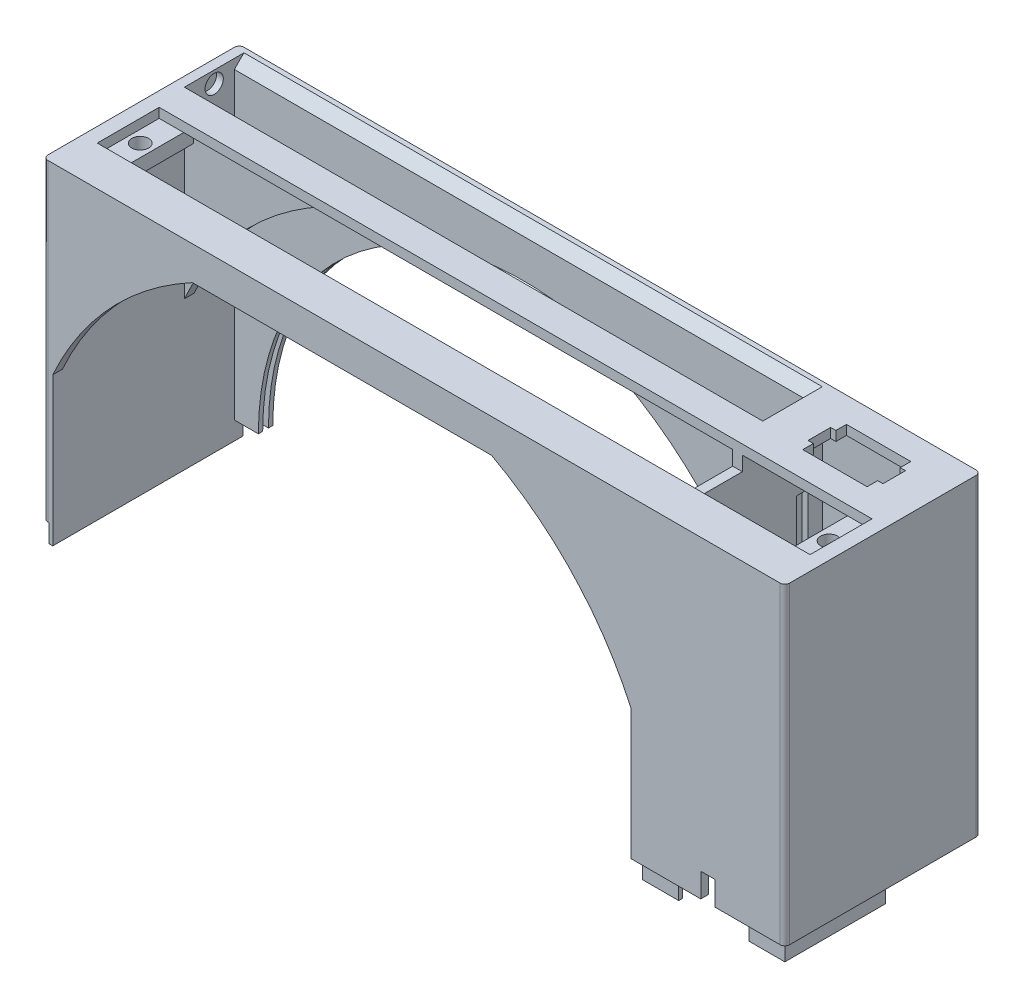
SolidWorks part; units mm, degrees
ref_plane "Plan de face" through (0, 0, 0) normal (0, 0, 1) x (1, 0, 0)
ref_plane "Plan de dessus" through (0, 0, 0) normal (0, 1, 0) x (1, 0, 0)
ref_plane "Plan de droite" through (0, 0, 0) normal (1, 0, 0) x (0, 0, -1)
sketch "Esquisse1" plane through (0, 0, 0) normal (0, 1, 0) x (1, 0, 0)
  line L1 (0, 0) -> (154.4, 0)
  line L2 (0, 0) -> (0, 40.8)
  line L3 (0, 40.8) -> (154.4, 40.8)
  line L4 (154.4, 0) -> (154.4, 40.8)
  dimension "D1" = 154.4
  dimension "D2" = 40.8
extrude "Boss.-Extru.1" add sketch "Esquisse1" against normal blind 2
sketch "Esquisse2" plane through (0, -2, 0) normal (0, -1, 0) x (1, 0, 0)
  line L0 (2, -2) -> (2, -27.4)
  line L1 (0, 0) -> (154.4, 0)
  line L2 (0, 0) -> (0, -40.8)
  line L3 (0, -40.8) -> (154.4, -40.8)
  line L4 (154.4, 0) -> (154.4, -40.8)
  line L7 (2, -2) -> (122.4, -2)
  line L8 (2, -29.4) -> (2, -37.8)
  line L9 (2, -29.4) -> (122.4, -29.4)
  line L11 (2, -27.4) -> (122.4, -27.4)
  line L13 (122.4, -27.4) -> (122.4, -2)
  line L14 (2, -2) -> (2, -38.8) construction
  line L16 (122.4, -37.8) -> (122.4, -29.4)
  line L19 (154.4, -40.8) -> (0, -40.8) construction
  line L20 (122.4, -37.8) -> (2, -37.8)
  line L21 (152.4, -2) -> (152.4, -38.8) construction
  line L22 (2, -2) -> (152.4, -2) construction
  line L23 (2, -38.8) -> (152.4, -38.8) construction
  line L24 (124.4, -37.8) -> (152.4, -37.8)
  line L25 (124.4, -37.8) -> (124.4, -2)
  line L26 (124.4, -2) -> (152.4, -2)
  line L27 (152.4, -37.8) -> (152.4, -2)
  dimension "D2" = 2
  dimension "D3" = 25.4
  dimension "D4" = 2
  dimension "D5" = 120.4
  dimension "D6" = 2
  dimension "D7" = 3
  dimension "D8" = 2
  dimension "D9" = 3
  dimension "D1" = 2
extrude "Boss.-Extru.2" add sketch "Esquisse2" along normal blind 63.2
sketch "Esquisse3" plane through (0, 0, 0) normal (0, 0, 1) x (1, 0, 0)
  line L0 (0, -65.2) -> (154.4, -65.2) construction
  line L1 (0, -65.2) -> (0, 0) construction
  line L4 (93.3249, -7) -> (31.0751, -7)
  line L7 (122.4, -65.2) -> (2, -65.2)
  line L8 (2, -38.1452) -> (2, -65.2)
  line L9 (62.2, -65.2) -> (62.2, -7) construction
  line L10 (122.4, -38.1452) -> (122.4, -65.2)
  arc A0 (31.0751, -7) -> (2, -38.1452) centre (62.2, -65.2) ccw
  arc A1 (122.4, -38.1452) -> (93.3249, -7) centre (62.2, -65.2) ccw
  point P13 (62.2, 0.8)
  dimension "D1" = 132
  dimension "D2" = 60.2
  dimension "D3" = 2
  dimension "D4" = 58.2
extrude "Enlèv. mat.-Extru.1" cut sketch "Esquisse3" against normal up to surface (29.4 mm away) up to face at (62.2, -33.6, -29.4)
sketch "Esquisse8" plane through (0, 0, -2) normal (0, 0, -1) x (-1, 0, 0)
  line L0 (-152.4, -65.2) -> (-152.4, -2) construction
  line L1 (-142.9, -56.4) -> (-133.9, -56.4)
  line L2 (-142.9, -56.4) -> (-142.9, -65.2)
  line L3 (-142.9, -65.2) -> (-133.9, -65.2)
  line L4 (-133.9, -56.4) -> (-133.9, -65.2)
  line L6 (-152.4, -65.2) -> (-124.4, -65.2) construction
  dimension "D1" = 9.5
  dimension "D2" = 9
  dimension "D3" = 8.8
extrude "Enlèv. mat.-Extru.3" cut sketch "Esquisse8" against normal blind 0.4
sketch "Esquisse9" plane through (0, 0, -1.6) normal (0, 0, -1) x (-1, 0, 0)
  line L0 (-142.9, -65.2) -> (-133.9, -65.2) construction
  line L1 (-139.9, -65.2) -> (-136.9, -65.2)
  line L2 (-139.9, -65.2) -> (-139.9, -60.2)
  line L3 (-139.9, -60.2) -> (-136.9, -60.2)
  line L4 (-136.9, -65.2) -> (-136.9, -60.2)
  point P8 (-138.4, -65.2)
  point P9 (-138.4, -65.2)
  dimension "D1" = 5
  dimension "D2" = 3
extrude "Enlèv. mat.-Extru.4" cut sketch "Esquisse9" against normal through all
sketch "Esquisse10" plane through (0, -65.2, 0) normal (0, -1, 0) x (1, 0, 0)
  line L0 (152.4, -37.8) -> (152.4, -2) construction
  line L1 (124.4, -37.8) -> (152.4, -37.8) construction
  line L2 (152.4, -34.8) -> (153.6, -34.8)
  line L3 (152.4, -34.8) -> (152.4, -32.4)
  line L4 (152.4, -32.4) -> (153.6, -32.4)
  line L5 (153.6, -34.8) -> (153.6, -32.4)
  line L6 (138.4, -37.8) -> (138.4, -40.8) construction
  line L7 (0, -40.8) -> (154.4, -40.8) construction
  line L8 (123.2, -34.8) -> (123.2, -32.4)
  line L9 (124.4, -32.4) -> (123.2, -32.4)
  line L10 (124.4, -34.8) -> (124.4, -32.4)
  line L11 (124.4, -34.8) -> (123.2, -34.8)
  dimension "D1" = 2.4
  dimension "D2" = 3
  dimension "D3" = 1.2
extrude "Enlèv. mat.-Extru.5" cut sketch "Esquisse10" against normal blind 50.2
sketch "Esquisse12" plane through (0, -65.2, 0) normal (0, -1, 0) x (1, 0, 0)
  line L6 (1.2, -39.6) -> (2, -39.6)
  line L7 (152.4, -32.4) -> (152.4, -2) construction
  line L9 (1.2, -39.6) -> (1.2, 0)
  line L10 (1.2, 0) -> (2, 0)
  line L11 (2, -39.6) -> (2, 0)
  line L12 (152.4, -22.2) -> (153.2, -22.2)
  line L13 (152.4, -22.2) -> (152.4, -2)
  line L14 (152.4, -1.2) -> (153.2, -1.2)
  line L15 (153.2, -22.2) -> (153.2, -1.2)
  line L16 (152.4, -2) -> (142.9, -2) construction
  line L17 (153.2, -1.2) -> (145.7, -1.2)
  line L18 (153.2, -1.2) -> (153.2, -2)
  line L19 (152.4, -2) -> (145.7, -2)
  line L20 (145.7, -1.2) -> (145.7, -2)
  line L21 (152.4, -2) -> (124.4, -2) construction
  line L22 (138.4, -2) -> (138.4, -40.8) construction
  line L23 (0, -40.8) -> (154.4, -40.8) construction
  line L24 (131.1, -1.2) -> (131.1, -2)
  line L25 (124.4, -2) -> (131.1, -2)
  line L26 (123.6, -1.2) -> (123.6, -2)
  line L27 (123.6, -1.2) -> (131.1, -1.2)
  line L28 (123.6, -22.2) -> (123.6, -1.2)
  line L29 (124.4, -1.2) -> (123.6, -1.2)
  line L30 (124.4, -22.2) -> (124.4, -2)
  line L31 (124.4, -22.2) -> (123.6, -22.2)
  line L33 (2, -37.8) -> (122.4, -37.8) construction
  dimension "D1" = 1.8
  dimension "D2" = 0.8
  dimension "D4" = 21
  dimension "D5" = 0.8
  dimension "D6" = 0.8
  dimension "D7" = 7.5
extrude "Boss.-Extru.3" add sketch "Esquisse12" along normal blind 3.8
sketch "Esquisse14" plane through (0, 0, 0) normal (0, 1, 0) x (1, 0, 0)
  line L6 (154.4, 40.8) -> (0, 40.8) construction
  line L7 (2, 37.8) -> (122.4, 37.8)
  line L8 (2, 37.8) -> (2, 29.4)
  line L9 (2, 29.4) -> (122.4, 29.4)
  line L10 (122.4, 37.8) -> (122.4, 29.4)
  line L11 (0, 40.8) -> (0, 0) construction
  dimension "D1" = 8.4
  dimension "D2" = 120.4
  dimension "D3" = 3
  dimension "D4" = 2
extrude "Enlèv. mat.-Extru.6" cut sketch "Esquisse14" against normal up to next
sketch "Esquisse16" plane through (0, 0, 0) normal (0, 1, 0) x (1, 0, 0)
  line L0 (122.4, 29.4) -> (122.4, 0) construction
  line L1 (3, 21.15) -> (151.4, 21.15)
  line L2 (3, 21.15) -> (3, 8.25)
  line L3 (3, 8.25) -> (151.4, 8.25)
  line L4 (151.4, 21.15) -> (151.4, 8.25)
  line L5 (154.4, 0) -> (0, 0) construction
  point P8 (77.2, 8.25)
  point P11 (122.4, 14.7)
  point P12 (151.4, 14.7)
  point P13 (77.2, 0)
  dimension "D1" = 12.9
  dimension "D2" = 148.4
extrude "Enlèv. mat.-Extru.8" cut sketch "Esquisse16" against normal blind 2
sketch "Esquisse17" plane through (0, -2, 0) normal (0, -1, 0) x (1, 0, 0)
  line L0 (2, -2) -> (2, -27.4) construction
  line L1 (8.1, -6.25) -> (2, -6.25)
  line L2 (8.1, -6.25) -> (8.1, -23.15)
  line L3 (8.1, -23.15) -> (2, -23.15)
  line L4 (2, -6.25) -> (2, -23.15)
  line L5 (3, -8.25) -> (3, -21.15) construction
  line L6 (3, -21.15) -> (3, -8.25) construction
  line L7 (3, -8.25) -> (122.4, -8.25) construction
  line L8 (8, -21.15) -> (8, -8.25) construction
  line L9 (3, -21.15) -> (151.4, -21.15) construction
  line L10 (77.2, -21.15) -> (77.2, -8.25) construction
  line L11 (151.4, -8.25) -> (146.4, -8.25) construction
  line L12 (146.4, -21.15) -> (146.4, -8.25) construction
  line L17 (3, -8.25) -> (8, -8.25) construction
  line L18 (151.4, -8.25) -> (151.4, -21.15) construction
  line L19 (152.4, -6.25) -> (152.4, -23.15)
  line L20 (146.3, -23.15) -> (152.4, -23.15)
  line L21 (146.3, -6.25) -> (146.3, -23.15)
  line L22 (146.3, -6.25) -> (152.4, -6.25)
  line L28 (62.2, -27.4) -> (62.2, -21.15) construction
  line L29 (2, -27.4) -> (122.4, -27.4) construction
  circle A0 centre (5.5, -14.7) radius 1.75
  circle A2 centre (148.9, -14.7) radius 1.75
  point P11 (2, -14.7)
  point P12 (3, -14.7)
  point P32 (5.5, -8.25)
  dimension "D3" = 3.5
  dimension "D1" = 2
  dimension "D2" = 5.1
  dimension "D4" = 0.1
extrude "Boss.-Extru.5" add sketch "Esquisse17" along normal blind 3
sketch "Esquisse19" plane through (0, -2, 0) normal (0, 1, 0) x (1, 0, 0)
  line L1 (146.3, 21.15) -> (8.1, 21.15)
  line L2 (146.3, 21.15) -> (146.3, 8.25)
  line L3 (146.3, 8.25) -> (8.1, 8.25)
  line L4 (8.1, 21.15) -> (8.1, 8.25)
extrude "Enlèv. mat.-Extru.10" cut sketch "Esquisse19" against normal blind 3
sketch "Esquisse20" plane through (122.4, 0, 0) normal (-1, 0, 0) x (0, 0, 1)
  line L0 (-29.4, -38.1452) -> (-29.4, 0) construction
  line L1 (-37.8, 0) -> (-29.4, 0)
  line L2 (-37.8, 0) -> (-37.8, -5)
  line L3 (-37.8, -5) -> (-29.4, -5)
  line L4 (-29.4, 0) -> (-29.4, -5)
  line L5 (-29.4, -5) -> (-37.8, 0) construction
  line L6 (-37.8, -65.2) -> (-37.8, 0) construction
  line L7 (-37.8, 0) -> (-40.7854, 0) construction
  circle A0 centre (-33.6, -2.5) radius 1.9
  dimension "D2" = 3.8
  dimension "D1" = 5
extrude "Enlèv. mat.-Extru.11" cut sketch "Esquisse20" against normal blind 1.4 contours A0
sketch "Esquisse21" plane through (2, 0, 0) normal (1, 0, 0) x (0, 0, -1)
  line L1 (29.4, 0) -> (37.8, 0)
  line L2 (29.4, 0) -> (29.4, -5)
  line L3 (29.4, -5) -> (37.8, -5)
  line L4 (37.8, 0) -> (37.8, -5)
  line L5 (29.4, 0) -> (37.8, -5) construction
  line L6 (37.8, -65.2) -> (37.8, 0) construction
  circle A0 centre (33.6, -2.5) radius 1.9
  dimension "D2" = 3.8
  dimension "D1" = 5
extrude "Enlèv. mat.-Extru.12" cut sketch "Esquisse21" against normal blind 1.4 contours L5 A0 | A0 L5 region at (2, -1.8071, -34.0125) region at (2, -3.1929, -33.1875)
sketch "Esquisse22" plane through (0, 0, -40.8) normal (0, 0, -1) x (-1, 0, 0)
  line L0 (0, -65.2) -> (-124.4, -65.2) construction
  line L1 (0, -65.2) -> (-154.4, -65.2) construction
  circle A0 centre (-62.2, -65.2) radius 55.2
  point P7 (-62.2, -65.2)
  dimension "D1" = 110.4
  dimension "D2" = 124.4
extrude "Enlèv. mat.-Extru.13" cut sketch "Esquisse22" against normal up to next
sketch "Esquisse23" plane through (0, 0, -40.8) normal (0, 0, -1) x (-1, 0, 0)
  circle A0 centre (-62.2, -65.2) radius 58.2
  arc A1 (-7, -65.2) -> (-117.4, -65.2) centre (-62.2, -65.2) ccw construction
  dimension "D1" = 3
extrude "Enlèv. mat.-Extru.14" cut sketch "Esquisse23" against normal blind 1.2 from offset 0.9 offset against normal yes
sketch "Esquisse24" plane through (0, 0, 0) normal (0, 1, 0) x (1, 0, 0)
  line L3 (138.4, 40.8) -> (138.4, 21.15) construction
  line L4 (151.4, 21.15) -> (3, 21.15) construction
  line L8 (154.4, 40.8) -> (122.4, 40.8) construction
  line L9 (154.4, 0) -> (154.4, 40.8) construction
  line L10 (122.4, 29.4) -> (122.4, 37.8) construction
  line L11 (154.4, 40.8) -> (0, 40.8) construction
  line L20 (145.1, 26.425) -> (131.7, 35.525) construction
  line L21 (131.7, 35.525) -> (145.1, 35.525)
  line L22 (131.7, 35.525) -> (131.7, 33.325)
  line L23 (131.7, 26.425) -> (145.1, 26.425)
  line L24 (145.1, 35.525) -> (145.1, 26.425)
  line L25 (130.6, 33.325) -> (130.6, 28.625)
  line L26 (145.1, 33.325) -> (146.2, 33.325)
  line L27 (145.1, 33.325) -> (145.1, 28.625)
  line L28 (145.1, 28.625) -> (146.2, 28.625)
  line L29 (146.2, 33.325) -> (146.2, 28.625)
  line L30 (131.7, 28.625) -> (130.6, 28.625)
  line L32 (131.7, 33.325) -> (130.6, 33.325)
  line L33 (131.7, 28.625) -> (131.7, 26.425)
  point P8 (138.4, 30.975)
  point P9 (138.4, 30.975)
  point P14 (145.1, 30.975)
  point P15 (145.1, 30.975)
  dimension "D1" = 13.4
  dimension "D2" = 9.1
  dimension "D3" = 1.1
  dimension "D4" = 4.7
extrude "Enlèv. mat.-Extru.16" cut sketch "Esquisse24" against normal up to next contours L30 L33 L23 L24 L21 L22 L32 L25 | L29 L26 L24 L28 region at (138.1051, 0, -30.975) region at (145.65, 0, -30.975)
sketch "Esquisse27" plane through (0, 0, -37.8) normal (0, 0, 1) x (1, 0, 0)
  line L0 (124.4, -65.2) -> (152.4, -65.2) construction
  line L2 (151.4, -62.2) -> (125.4, -62.2)
  line L3 (151.4, -62.2) -> (151.4, -65.2)
  line L4 (151.4, -65.2) -> (125.4, -65.2)
  line L5 (125.4, -62.2) -> (125.4, -65.2)
  point P8 (138.4, -65.2)
  point P9 (138.4, -65.2)
  dimension "D1" = 26
  dimension "D2" = 3
extrude "Enlèv. mat.-Extru.17" cut sketch "Esquisse27" against normal blind 1.2 from offset 0.9 offset against normal yes
fillet "Congé1" radius 1 4 edges at (0, -32.6, 0) (0, -32.6, -40.8) (154.4, -32.6, -40.8) (154.4, -32.6, 0)
chamfer "Chanfrein1" distance 2 angle 45 2 edges at (62.2, 0, -29.4) (62.2, 0, -37.8)
